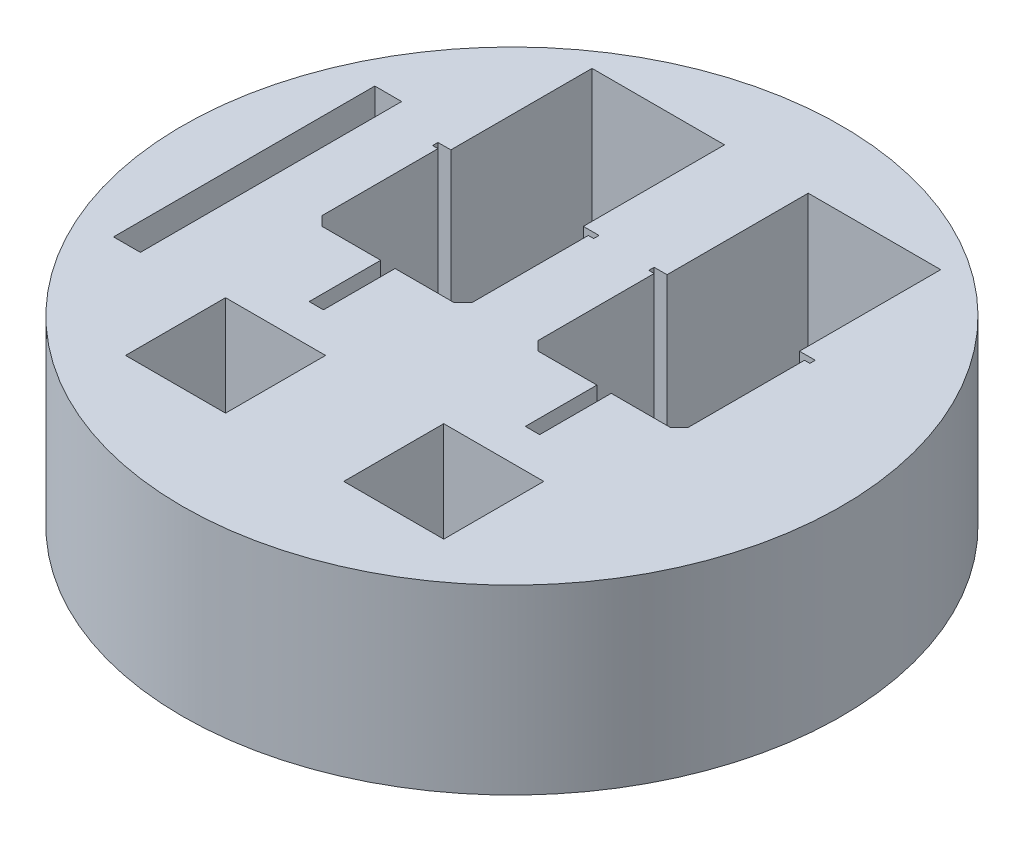
SolidWorks part; units mm, degrees
material "Polyurethane Foam Flexible"
ref_plane "Front Plane" through (0, 0, 0) normal (0, 0, 1) x (1, 0, 0)
ref_plane "Top Plane" through (0, 0, 0) normal (0, 1, 0) x (1, 0, 0)
ref_plane "Right Plane" through (0, 0, 0) normal (1, 0, 0) x (0, 0, -1)
sketch "Sketch1" plane through (0, 0, 0) normal (0, 1, 0) x (1, 0, 0)
  circle A0 centre (0, 0) radius 92.075
  dimension "D1" = 184.15
extrude "Boss-Extrude1" add sketch "Sketch1" along normal blind 50.8
sketch "Sketch4" plane through (0, 0, 0) normal (0, 1, 0) x (1, 0, 0)
  line L0 (0, 0) -> (0, 16.6464) construction
  line L1 (-55.88, 71.12) -> (-5.08, 71.12)
  line L2 (-55.88, 71.12) -> (-55.88, -25.4)
  line L3 (-55.88, -25.4) -> (-5.08, -25.4)
  line L4 (-5.08, 71.12) -> (-5.08, -25.4)
  line L5 (55.88, 71.12) -> (5.08, 71.12)
  line L6 (5.08, 71.12) -> (5.08, -25.4)
  line L7 (55.88, -25.4) -> (5.08, -25.4)
  line L8 (55.88, 71.12) -> (55.88, -25.4)
  dimension "D1" = 5.08
  dimension "D2" = 96.52
  dimension "D3" = 71.12
  dimension "D4" = 50.8
extrude "Cut-Extrude3" [suppressed] cut sketch "Sketch4" along normal up to surface (50.8 mm away) up to face at (0, 50.8, 92.075)
sketch "Sketch6" plane through (0, 0, 0) normal (0, -1, 0) x (1, 0, 0)
  line L1 (-44.45, -63.5) -> (-16.51, -63.5) construction
  line L2 (-44.45, -63.5) -> (-44.45, -35.56) construction
  line L3 (-44.45, -35.56) -> (-16.51, -35.56) construction
  line L4 (-16.51, -63.5) -> (-16.51, -35.56) construction
  line L5 (0, 0) -> (0, -11.8444) construction
  line L6 (44.45, -63.5) -> (44.45, -35.56) construction
  line L7 (44.45, -63.5) -> (16.51, -63.5) construction
  line L8 (16.51, -63.5) -> (16.51, -35.56) construction
  line L9 (44.45, -35.56) -> (16.51, -35.56) construction
  line L10 (0, 0) -> (-75.2732, 0) construction
  line L11 (44.45, 63.5) -> (16.51, 63.5)
  line L12 (44.45, 63.5) -> (44.45, 35.56)
  line L13 (-44.45, 35.56) -> (-16.51, 35.56)
  line L14 (44.45, 35.56) -> (16.51, 35.56)
  line L15 (16.51, 63.5) -> (16.51, 35.56)
  line L16 (-16.51, 63.5) -> (-16.51, 35.56)
  line L17 (-44.45, 63.5) -> (-16.51, 63.5)
  line L18 (-44.45, 63.5) -> (-44.45, 35.56)
  dimension "D1" = 27.94
  dimension "D2" = 27.94
  dimension "D3" = 35.56
  dimension "D4" = 16.51
extrude "Cut-Extrude4" cut sketch "Sketch6" against normal up to surface (50.8 mm away) up to face at (0, 50.8, 92.075)
sketch "Sketch8" plane through (0, 50.8, 0) normal (0, 1, 0) x (1, 0, 0)
  line L0 (48.6732, 66.9206) -> (48.6732, 31.675)
  line L1 (48.6732, 31.675) -> (53.066, 31.675)
  line L2 (53.066, 31.675) -> (53.066, 30.175)
  line L3 (53.066, 30.175) -> (51.5683, 30.175)
  line L4 (51.5683, 30.175) -> (51.5683, -2.285)
  line L5 (51.5683, -2.285) -> (49.0283, -4.825)
  line L6 (49.0283, -4.825) -> (32.5683, -4.825)
  line L7 (32.5683, -4.825) -> (32.5683, -24.825)
  line L8 (32.5683, -24.825) -> (28.5683, -24.825)
  line L9 (28.5683, -24.825) -> (28.5683, -4.825)
  line L10 (28.5683, -4.825) -> (12.1083, -4.825)
  line L11 (12.1083, -4.825) -> (9.5683, -2.285)
  line L12 (9.5683, -2.285) -> (9.5683, 30.175)
  line L13 (9.5683, 30.175) -> (8.066, 30.175)
  line L14 (8.066, 30.175) -> (8.066, 31.675)
  line L15 (8.066, 31.675) -> (10.8383, 31.675)
  line L16 (11.6589, 66.9206) -> (11.6589, 31.675)
  line L17 (11.6589, 31.675) -> (10.8383, 31.675)
  line L18 (11.6589, 66.9206) -> (11.6589, 71.12)
  line L20 (11.6589, 71.12) -> (48.6732, 71.12)
  line L21 (48.6732, 71.12) -> (48.6732, 66.9206)
  line L22 (-8.8317, -2.285) -> (-11.3717, -4.825)
  line L23 (-11.3717, -4.825) -> (-27.8317, -4.825)
  line L24 (-27.8317, -4.825) -> (-27.8317, -24.825)
  line L25 (-27.8317, -24.825) -> (-31.8317, -24.825)
  line L26 (-31.8317, -24.825) -> (-31.8317, -4.825)
  line L27 (-31.8317, -4.825) -> (-48.2917, -4.825)
  line L28 (-48.2917, -4.825) -> (-50.8317, -2.285)
  line L29 (-50.8317, -2.285) -> (-50.8317, 30.175)
  line L30 (-50.8317, 30.175) -> (-52.334, 30.175)
  line L31 (-52.334, 30.175) -> (-52.334, 31.675)
  line L32 (-52.334, 31.675) -> (-48.7411, 31.675)
  line L33 (-48.7411, 66.9206) -> (-48.7411, 31.675)
  line L34 (-8.8317, -2.285) -> (-8.8317, 30.175)
  line L35 (-8.8317, 30.175) -> (-7.334, 30.175)
  line L36 (-7.334, 30.175) -> (-7.334, 31.675)
  line L37 (-11.7268, 66.9206) -> (-11.7268, 31.675)
  line L38 (-11.7268, 31.675) -> (-7.334, 31.675)
  line L39 (-11.7268, 66.9206) -> (-11.7268, 71.12)
  line L41 (-11.7268, 71.12) -> (-48.7411, 71.12)
  line L42 (-48.7411, 71.12) -> (-48.7411, 66.9206)
extrude "Cut-Extrude5" cut sketch "Sketch8" against normal up to surface (50.8 mm away) up to face at (-30.48, 0, 49.53)
sketch "Sketch9" plane through (0, 50.8, 0) normal (0, 1, 0) x (1, 0, 0)
  line L0 (0, 0) -> (-67.31, 0) construction
  line L1 (-74.81, 36.5) -> (-67.31, 36.5)
  line L2 (-74.81, 36.5) -> (-74.81, -36.5)
  line L3 (-74.81, -36.5) -> (-67.31, -36.5)
  line L4 (-67.31, 36.5) -> (-67.31, -36.5)
  point P7 (-67.31, 0)
  dimension "D1" = 73
  dimension "D2" = 7.5
  dimension "D3" = 67.31
extrude "Cut-Extrude6" cut sketch "Sketch9" against normal up to surface (50.8 mm away) up to face at (-29.9216, 0, -17.5622)
